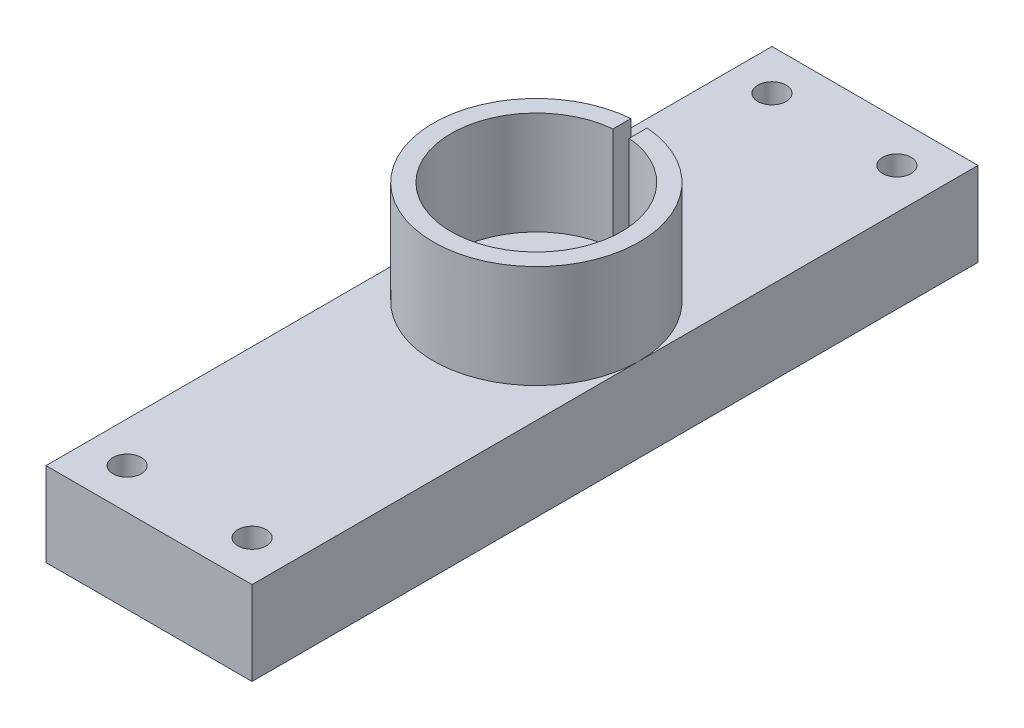
SolidWorks part; units mm, degrees
ref_plane "Front Plane" through (0, 0, 0) normal (0, 0, 1) x (1, 0, 0)
ref_plane "Top Plane" through (0, 0, 0) normal (0, 1, 0) x (1, 0, 0)
ref_plane "Right Plane" through (0, 0, 0) normal (1, 0, 0) x (0, 0, -1)
sketch "Sketch1" plane through (0, 0, 0) normal (0, 1, 0) x (1, 0, 0)
  line L1 (0, 0) -> (25.4, 0)
  line L2 (0, 0) -> (0, 89.5)
  line L3 (0, 89.5) -> (25.4, 89.5)
  line L4 (25.4, 0) -> (25.4, 89.5)
  circle A0 centre (5, 84.5) radius 1.75
  circle A1 centre (20.4, 84.5) radius 1.75
  circle A2 centre (5, 5) radius 1.75
  circle A3 centre (20.4, 5) radius 1.75
  dimension "D3" = 3.5
  dimension "D1" = 89.5
  dimension "D2" = 25.4
  dimension "D4" = 5
  dimension "D5" = 5
  dimension "D6" = 5
  dimension "D7" = 5
extrude "Boss-Extrude1" add sketch "Sketch1" along normal blind 10.35
sketch "Sketch2" plane through (0, 10.35, 0) normal (0, 1, 0) x (1, 0, 0)
  line L1 (25.4, 89.5) -> (0, 89.5) construction
  circle A0 centre (12.7, 47.75) radius 12.7
  circle A1 centre (12.7, 47.75) radius 10.5
  point P2 (12.7, 89.5)
  dimension "D1" = 41.75
  dimension "D2" = 25.4
  dimension "D3" = 21
extrude "Boss-Extrude2" add sketch "Sketch2" along normal blind 12.7
ref_plane "Plane1" through (0, 0, -35.05) normal (0, 0, 1) x (0, -1, 0)
sketch "Sketch5" plane through (0, 23.05, 0) normal (0, 1, 0) x (1, 0, 0)
  line L1 (11.7, 62.7043) -> (13.7, 62.7043)
  line L2 (11.7, 62.7043) -> (11.7, 54.6968)
  line L3 (11.7, 54.6968) -> (13.7, 54.6968)
  line L4 (13.7, 62.7043) -> (13.7, 54.6968)
  circle A0 centre (12.7, 47.75) radius 10.5 construction
  dimension "D1" = 1
  dimension "D2" = 2
extrude "Cut-Extrude1" cut sketch "Sketch5" against normal up to surface (12.7 mm away) up to face at (12.7, 10.35, -71.8)
sketch "Sketch6" plane through (0, 10.35, 0) normal (0, 1, 0) x (1, 0, 0)
  circle A0 centre (12.7, 47.75) radius 6.25
  dimension "D1" = 12.5
extrude "Cut-Extrude2" cut sketch "Sketch6" against normal blind 4
sketch "Sketch7" plane through (0, 6.35, 0) normal (0, 1, 0) x (1, 0, 0)
  circle A0 centre (12.7, 47.75) radius 2
  dimension "D1" = 4
extrude "Cut-Extrude3" cut sketch "Sketch7" against normal up to surface (6.35 mm away) up to face at (5, 0, -3.25)
